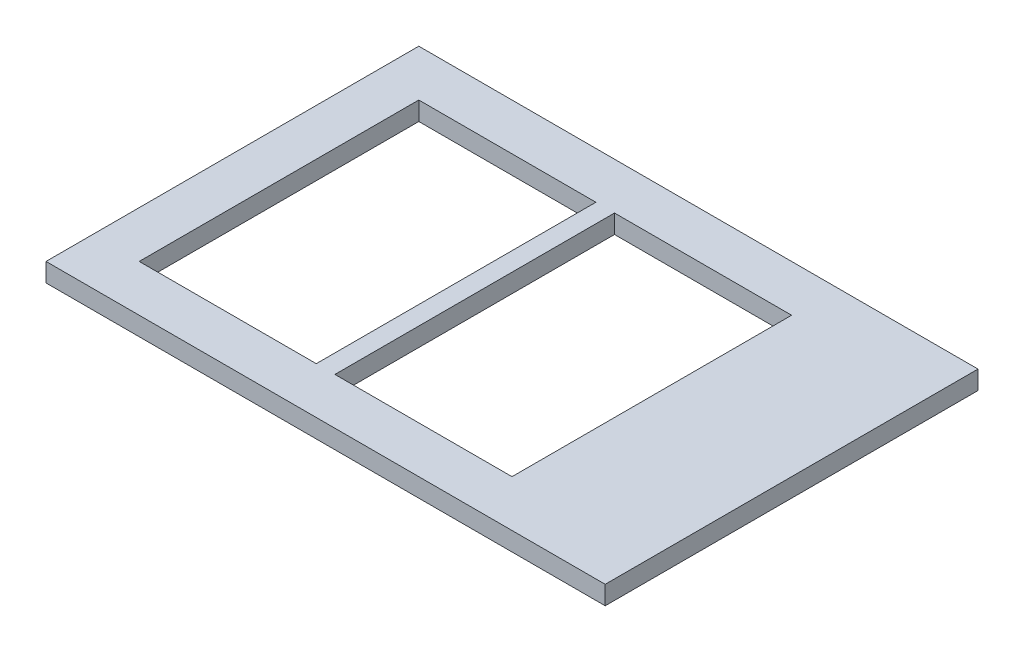
SolidWorks part; units mm, degrees
ref_plane "Front Plane" through (0, 0, 0) normal (0, 0, 1) x (1, 0, 0)
ref_plane "Top Plane" through (0, 0, 0) normal (0, 1, 0) x (1, 0, 0)
ref_plane "Right Plane" through (0, 0, 0) normal (1, 0, 0) x (0, 0, -1)
sketch "Sketch1" plane through (0, 0, 0) normal (0, 1, 0) x (1, 0, 0)
  line L0 (-270, 170) -> (170, 170)
  line L5 (-300, -200) -> (300, -200)
  line L6 (-300, -200) -> (-300, 200)
  line L7 (-300, 200) -> (300, 200)
  line L8 (300, -200) -> (300, 200)
  line L9 (170, -150) -> (170, 150)
  line L14 (-250, 150) -> (250, 150) construction
  line L16 (-270, -170) -> (170, -170)
  line L17 (-270, -170) -> (-270, 170)
  line L18 (-250, -150) -> (-250, 150)
  line L19 (-250, 150) -> (-60, 150)
  line L21 (-250, -150) -> (-60, -150)
  line L22 (-60, -150) -> (-60, 150)
  line L23 (-40, -150) -> (-40, 150)
  line L24 (150, -150) -> (150, 150)
  line L25 (250, -150) -> (250, 150) construction
  line L26 (-250, -150) -> (250, -150) construction
  line L27 (170, 170) -> (170, 150)
  line L28 (170, -150) -> (170, -170)
  line L29 (-40, 150) -> (150, 150)
  line L30 (-270, 170) -> (270, 170) construction
  line L31 (270, -170) -> (270, 170) construction
  line L32 (-270, -170) -> (270, -170) construction
  line L33 (-40, -150) -> (150, -150)
  point P0 (0, 0)
  dimension "D1" = 20
  dimension "D2" = 130
extrude "Boss-Extrude2" add sketch "Sketch1" along normal blind 20 contours L5 L8 L7 L6 L9 L28 L16 L17 L0 L27 region at (-292.7889, 0, 0)
extrude "Boss-Extrude5" add sketch "Sketch1<10>" along normal blind 20 contours L28 L9 L27 L0 L17 L16 L33 L23 L29 L24 L22 L21 L18 L19 region at (-50, 0, 0)
sketch "Sketch1<10>" plane through (0, 0, 0) normal (0, 1, 0) x (1, 0, 0) same geometry as "Sketch1"
